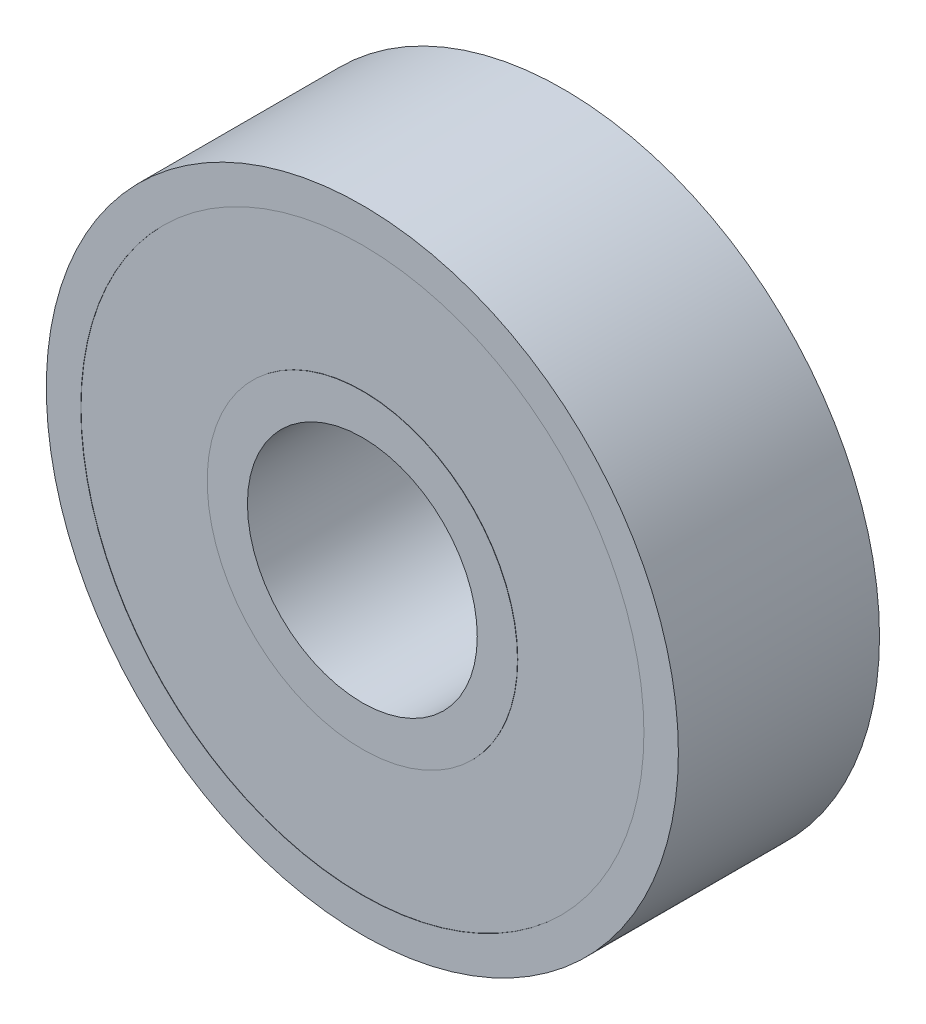
SolidWorks part; units mm, degrees
ref_plane "Front Plane" through (0, 0, 0) normal (0, 0, 1) x (1, 0, 0)
ref_plane "Top Plane" through (0, 0, 0) normal (0, 1, 0) x (1, 0, 0)
ref_plane "Right Plane" through (0, 0, 0) normal (1, 0, 0) x (0, 0, -1)
sketch "Sketch1" plane through (0, 0, 0) normal (0, 0, 1) x (1, 0, 0)
  circle A0 centre (0, 0) radius 4
  circle A1 centre (0, 0) radius 5.4
  circle A2 centre (0, 0) radius 9.8
  circle A3 centre (0, 0) radius 11
  dimension "D1" = 22
  dimension "D2" = 8
  dimension "D3" = 1.4
  dimension "D4" = 1.2
extrude "Boss-Extrude1" add sketch "Sketch1" along normal blind 7 contours A3 A2 | A1 A0 region at (-5.2473, 0, 0) region at (-10.6889, 0, 0)
extrude "Boss-Extrude2" add sketch "Sketch1<3>" along normal blind 6.98 from offset 0.01 contours A2 A1 region at (-9.5228, 0, 0)
sketch "Sketch1<3>" plane through (0, 0, 0) normal (0, 0, 1) x (1, 0, 0) same geometry as "Sketch1"
